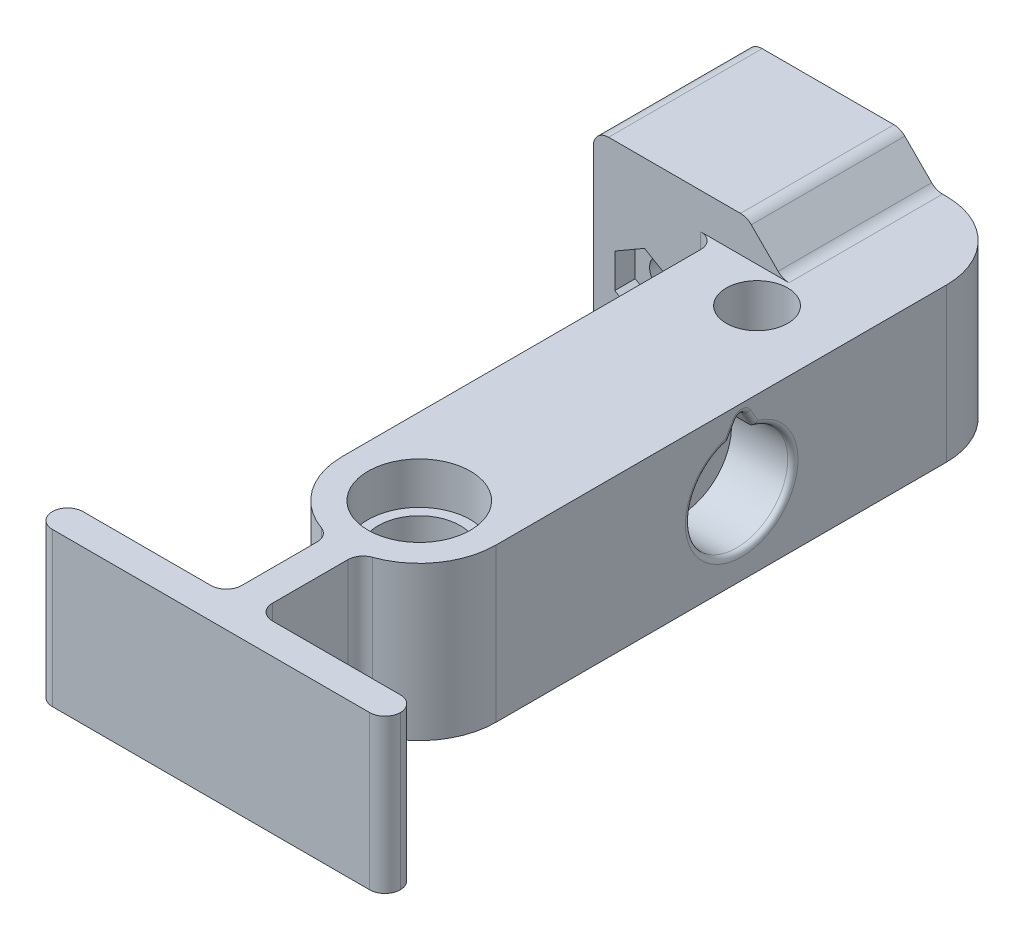
SolidWorks part; units mm, degrees
ref_plane "Front Plane" through (0, 0, 0) normal (0, 0, 1) x (1, 0, 0)
ref_plane "Top Plane" through (0, 0, 0) normal (0, 1, 0) x (1, 0, 0)
ref_plane "Right Plane" through (0, 0, 0) normal (1, 0, 0) x (0, 0, -1)
sketch "Sketch1" plane through (0, 0, 0) normal (0, 1, 0) x (1, 0, 0)
  line L0 (0, 22) -> (0, -22) construction
  line L1 (-7.5, 22) -> (7.5, 22)
  line L2 (-7.5, 22) -> (-7.5, -22)
  line L3 (-7.5, -22) -> (7.5, -22)
  line L4 (7.5, 22) -> (7.5, -22)
  line L5 (-7.5, 22) -> (7.5, -22) construction
  line L6 (-7.5, -22) -> (7.5, 22) construction
  circle A0 centre (0, -14.5) radius 4
  circle A1 centre (0, -14.5) radius 7.5
  point P0 (0, 0)
  dimension "D1" = 8
  dimension "D2" = 15
  dimension "D4" = 44
extrude "Boss-Extrude1" add sketch "Sketch1" along normal mid plane 15 contours L2 | L4 | A1 L4 L1 L2 | A1 A0 | L3 region at (0, 0, -6.6495) region at (0, 0, 7.2121)
sketch "Sketch2" plane through (0, 7.5, 0) normal (0, 1, 0) x (1, 0, 0)
  circle A0 centre (0, -14.5) radius 5
  dimension "D1" = 10
extrude "Cut-Extrude1" cut sketch "Sketch2" against normal blind 4.1
mirror "Mirror1" about plane through (0, 0, 0) normal (0, 1, 0) of "Cut-Extrude1"
sketch "Sketch12" plane through (0, -3.4, 0) normal (0, -1, 0) x (1, 0, 0)
  circle A0 centre (0, 14.5) radius 4 construction
  circle A1 centre (0, 14.5) radius 5
  circle A2 centre (0, 14.5) radius 5
  circle A3 centre (0, 14.5) radius 4
  dimension "D1" = 0
extrude "Cut-Extrude10" cut sketch "Sketch12" against normal blind 0.5
sketch "Sketch4" plane through (7.5, 0, 0) normal (1, 0, 0) x (0, 0, -1)
  line L0 (-3.1918, 0) -> (3.917, 0) construction
  line L1 (8.25, 4.8412) -> (10.75, 4.8412) construction
  line L2 (-9.5, 7.5) -> (-19.5, 7.5) construction
  line L3 (-9.5, 7.5) -> (-19.5, 7.5)
  line L4 (-14.5, 7.5) -> (-14.5, -7.5) construction
  line L5 (22, -7.5) -> (-14.5, -7.5) construction
  line L6 (9.5, 0) -> (9.5, 7.5) construction
  line L9 (22, 7.5) -> (-14.5, 7.5) construction
  line L10 (9.5, 7.0063) -> (8.25, 4.8412)
  line L11 (9.5, 7.0063) -> (10.75, 4.8412)
  circle A1 centre (9.5, 0) radius 5
  circle A3 centre (9.5, 6.0063) radius 0.5
  dimension "D1" = 24
  dimension "D2" = 10
  dimension "D5" = 1
  dimension "D4" = 2.5
extrude "Cut-Extrude3" cut sketch "Sketch4" against normal blind 6 contours A1 | A1 L11 L10 | A3 region at (7.5, 5.3219, -9.5) region at (7.5, 6.0063, -9.5) region at (7.5, 0, -9.5)
mirror "Mirror2" about plane through (0, 0, 0) normal (1, 0, 0) of "Cut-Extrude3"
sketch "Sketch18" plane through (0, -7.5, 0) normal (0, -1, 0) x (1, 0, 0)
  line L0 (0, -41.3409) -> (0, 22.3101) construction
  line L4 (7.5, -3.75) -> (-7.5, -3.75) construction
  line L5 (-19.5, -22) -> (-7.5, -22)
  line L6 (7.5, -29.5) -> (7.5, -22)
  line L7 (7.5, -22) -> (7.5, 14.5) construction
  line L8 (-7.5, -22) -> (7.5, -22)
  line L9 (-7.5, -22) -> (-7.5, 14.5) construction
  line L10 (0, -22) -> (0, -37) construction
  line L11 (0, -37) -> (-19.5, -37)
  line L13 (-19.5, -22) -> (-19.5, -37)
  circle A1 centre (0, -29.5) radius 7.5
  line M10 (-7.5, -22) -> (7.5, -22)
  dimension "D1" = 12
extrude "Boss-Extrude3" add sketch "Sketch18" against normal up to surface (15 mm away) contours A1 L6 L8 | A1 M10 | A1 | A1 L13 L11 region at (-12.5923, -7.5, -29.5) region at (5.8247, -7.5, -23.6753) region at (0, -7.5, -29.5) up to face at (0, 7.5, 19.5)
sketch "Sketch7" plane through (0, 7.5, 0) normal (0, 1, 0) x (1, 0, 0)
  line L0 (-19.5, 29.5) -> (7.5, 29.5) construction
  line L8 (7.5, 29.5) -> (7.5, -14.5) construction
  line L9 (-19.5, 28.05) -> (-9.5, 28.05)
  line L10 (-19.5, 28.05) -> (-19.5, 30.95)
  line L11 (-9.5, 28.05) -> (-9.5, 30.95)
  line L12 (-19.5, 30.95) -> (-9.5, 30.95)
  line L13 (-19.5, 28.05) -> (-9.5, 30.95) construction
  line L14 (-9.5, 28.05) -> (-19.5, 30.95) construction
  line L15 (-19.5, 22) -> (-19.5, 37) construction
  point P8 (-14.5, 29.5)
  dimension "D1" = 10
  dimension "D2" = 2.9
extrude "Cut-Extrude7" cut sketch "Sketch7" against normal up to next
sketch "Sketch8" plane through (-40.2452, 0, -37) normal (0, 0, 1) x (1, 0, 0)
  line L5 (20.7452, 0) -> (40.2452, 0) construction
  line L8 (20.7452, 7.5) -> (20.7452, -7.5) construction
  line L9 (40.2452, 7.5) -> (40.2452, -7.5) construction
  circle A2 centre (25.7452, 0) radius 1.5
  dimension "D2" = 5
  dimension "D3" = 3
extrude "Cut-Extrude8" cut sketch "Sketch8" along normal up to surface (15 mm away) contours A2
hole_wizard "CSK for M3 Flat Head Machine Screw1" positions "Sketch9" profile "Sketch10" countersink size "M3" standard "ANSI Metric"
sketch "Sketch9" plane through (-83.1458, 0, -37) normal (0, 0, 1) x (1, 0, 0)
  point P6 (68.6458, 0)
  point P17 (0, 0)
  point P18 (0, 0)
  point P19 (0, 0)
  point P20 (0, 0)
sketch "Sketch10" plane through (-14.5, 0, -37) normal (1, 0, 0) x (0, 1, 0)
  line L0 (0, 0) -> (0, 5.9013)
  line L1 (0, 5.9013) -> (1.5, 5)
  line L2 (1.5, 5) -> (1.5, 1.8)
  line L3 (1.5, 1.8) -> (3, 0.3)
  line L4 (3, 0.3) -> (3, 0)
  line L6 (3, 0) -> (0, 0)
  line L7 (-1.5, 1.8) -> (-3, 0.3) construction
  line L10 (0, 5.9013) -> (-1.5, 5) construction
  line L11 (0, -6.35) -> (0, 107.95) construction
  dimension "Hole Dia." = 3
  dimension "Hole Depth" = 5
  dimension "C'Sink Dia." = 6
  dimension "C'Sink Angle" = 90
  dimension "Drill Angle" = 118
  dimension "Head Clearance" = 0.3
sketch "Sketch11" plane through (15, 0, -22) normal (0, 0, 1) x (1, 0, 0)
  line L7 (-34.5, 7.5) -> (-34.5, -7.5) construction
  line L8 (-29.5, -3.3486) -> (-26.6, -1.6743)
  line L15 (-26.6, -1.6743) -> (-26.6, 1.6743)
  line L16 (-26.6, 1.6743) -> (-29.5, 3.3486)
  line L17 (-29.5, 3.3486) -> (-32.4, 1.6743)
  line L18 (-32.4, 1.6743) -> (-32.4, -1.6743)
  line L19 (-32.4, -1.6743) -> (-29.5, -3.3486)
  circle A0 centre (-29.5, 0) radius 2.9 construction
  dimension "D1" = 5.8
extrude "Cut-Extrude9" cut sketch "Sketch11" against normal blind 2
sketch "Sketch13" plane through (-44.6536, 0, -30.95) normal (0, 0, 1) x (1, 0, 0)
  line L0 (35.1536, -7.5) -> (35.1536, 7.5) construction
  line L2 (35.1536, -7.5) -> (35.1536, 7.5)
  line L3 (35.1536, 0) -> (44.6536, 0) construction
  line L4 (44.6536, 7.5) -> (44.6536, -7.5) construction
  line L5 (35.1536, 7.5) -> (42.6536, 0)
  line L6 (35.1536, -7.5) -> (42.6536, 0)
  dimension "D1" = 45
extrude "Cut-Extrude11" cut sketch "Sketch13" along normal up to surface (2.9 mm away) contours L5 L6 L2 up to face at (-13, 0, -28.05)
sketch "Sketch16" plane through (0, -7.5, 0) normal (0, -1, 0) x (1, 0, 0)
  line L0 (0, 42.718) -> (0, -5.4521) construction
  line L2 (-1.5, 31.8485) -> (1.5, 31.8485)
  line L3 (-1.5, 31.8485) -> (-1.5, 21.8485)
  line L4 (-1.5, 21.8485) -> (1.5, 21.8485)
  line L5 (1.5, 31.8485) -> (1.5, 21.8485)
  line L6 (-1.5, 31.8485) -> (1.5, 21.8485) construction
  line L7 (-1.5, 21.8485) -> (1.5, 31.8485) construction
  line L8 (-17, 34.8485) -> (17, 34.8485)
  line L9 (-17, 34.8485) -> (-17, 31.8485)
  line L10 (-17, 31.8485) -> (17, 31.8485)
  line L11 (17, 34.8485) -> (17, 31.8485)
  line L12 (-17, 34.8485) -> (17, 31.8485) construction
  line L13 (-17, 31.8485) -> (17, 34.8485) construction
  arc A0 (7.5, 14.5) -> (-7.5, 14.5) centre (0, 14.5) ccw construction
  point P1 (0, 26.8485)
  point P11 (0, 33.3485)
  arc M14 (7.5, 14.5) -> (-7.5, 14.5) centre (0, 14.5) ccw
  dimension "D1" = 3
  dimension "D2" = 10
  dimension "D3" = 34
extrude "Boss-Extrude2" add sketch "Sketch16" against normal up to surface (15 mm away) contours L5 L2 L3 M14 | L11 L8 L9 L10 L2 region at (0, -7.5, 33.3485) region at (0, -7.5, 26.899) up to face at (-8.677, 7.5, -20.9594)
sketch "Sketch19" plane through (0, -7.5, 0) normal (0, -1, 0) x (1, 0, 0)
  line L0 (0, 4.3088) -> (0, -5.4508) construction
  circle A0 centre (0, -18.5) radius 3
  circle A2 centre (0, 14.5) radius 5 construction
  dimension "D1" = 6
  dimension "D2" = 33
extrude "Cut-Extrude12" cut sketch "Sketch19" against normal up to next contours A0
sketch "Sketch20" plane through (0, 0, -37) normal (0, 0, -1) x (-1, 0, 0)
  line L0 (19.5, 7.5) -> (19.5, 11)
  line L1 (19.5, 11) -> (4.5, 11)
  line L2 (4.5, 11) -> (1, 7.5)
  line L3 (0, 7.5) -> (19.5, 7.5) construction
  line L4 (1, 7.5) -> (19.5, 7.5)
  point P3 (0, 0)
  point P8 (0, 0)
  dimension "D1" = 15
  dimension "D2" = 45
  dimension "D3" = 3.5
extrude "Boss-Extrude4" add sketch "Sketch20" against normal up to surface (15 mm away)
fillet "Fillet9" radius 0.5 8 edges at (-7.5, 5.5488, -10.3415) (-7.5, 6.5063, -9.5) (7.5, 5.5488, -8.6585) (7.5, 6.5063, -9.5) (-7.5, 5.5488, -8.6585) (-7.5, -5, -9.5) (7.5, 5.5488, -10.3415) (7.5, -5, -9.5)
fillet "Fillet8" radius 1.5 15 edges at (17, 0, 31.8485) (17, 0, 34.8485) (-17, 0, 34.8485) (-17, 0, 31.8485) (-1.5, 0, 31.8485) (-1.5, 0, 21.8485) (1.5, 0, 21.8485) (1.5, 0, 31.8485) (-19.5, -7.5, -25.025) (-19.5, -7.5, -33.975) (-7.5, 0, -22) (-2, 0, -29.5) (-1, 7.5, -29.5) (-4.5, 11, -29.5) (-19.5, 11, -29.5)
